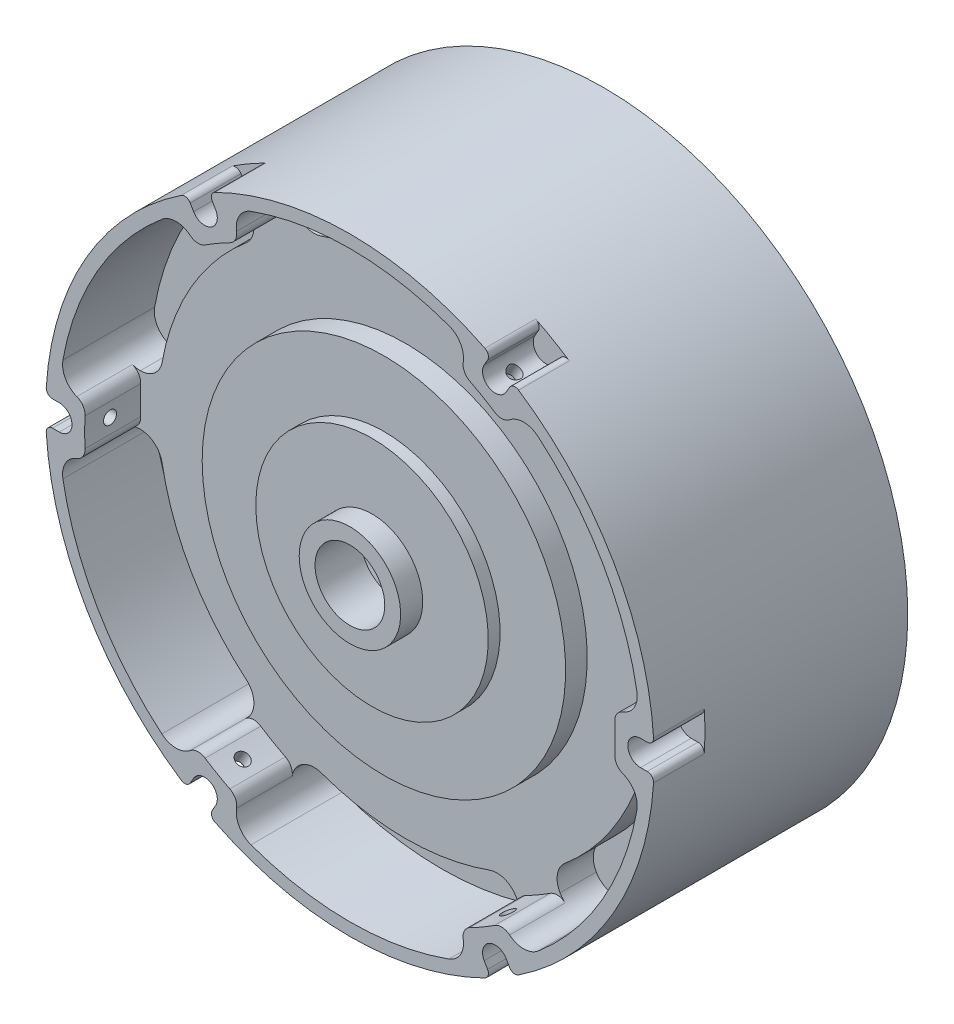
SolidWorks part; units mm, degrees
material "6061-T6 (SS)"
ref_plane "Front Plane" through (0, 0, 0) normal (0, 0, 1) x (1, 0, 0)
ref_plane "Top Plane" through (0, 0, 0) normal (0, 1, 0) x (1, 0, 0)
ref_plane "Right Plane" through (0, 0, 0) normal (1, 0, 0) x (0, 0, -1)
sketch "Sketch2" plane through (0, 0, 0) normal (0, 1, 0) x (1, 0, 0)
  line L0 (0, 11.176) -> (0, 0)
  line L2 (-76.2, 0) -> (-76.2, 46.101)
  line L3 (-76.2, 46.101) -> (-69.85, 46.101) construction
  line L4 (-69.85, 46.101) -> (-34.925, 46.101) construction
  line L5 (-34.925, 46.101) -> (0, 46.101) construction
  line L6 (-76.2, 0) -> (-73.025, 0)
  line L13 (-73.025, 0) -> (-73.025, 22.9805)
  line L14 (-73.025, 22.9805) -> (-61.9125, 22.9805)
  line L15 (-61.9125, 22.9805) -> (-61.9125, 13.9169)
  line L16 (-61.9125, 13.9169) -> (-45.5083, 13.9169)
  line L17 (-45.5083, 13.9169) -> (-45.5083, 8.5103)
  line L18 (-45.5083, 8.5103) -> (-29.1042, 8.5103)
  line L19 (-29.1042, 8.5103) -> (-29.1042, 5.5363)
  line L20 (0, 46.101) -> (0, 11.176) construction
  line L21 (-45.5083, 13.9169) -> (0, 46.101) construction
  line L22 (-61.9125, 22.9805) -> (0, 46.101) construction
  line L23 (0, 46.101) -> (-29.1042, 8.5103) construction
  line L24 (-29.1042, 5.5363) -> (-12.7, 5.5363)
  line L25 (-12.7, 5.5363) -> (-12.7, 0)
  line L26 (-12.7, 0) -> (0, 0)
  line L27 (0, 46.101) -> (-12.7, 5.5363) construction
  line L28 (-69.85, 46.101) -> (-69.85, 63.5)
  line L29 (-69.85, 63.5) -> (-76.2, 63.5)
  line L30 (-76.2, 63.5) -> (-76.2, 46.101)
  ellipse E0 centre (0, 46.101) end of major axis (69.85, 46.101) minor radius 34.925 construction
  ellipse E1 centre (0, 46.101) end of major axis (69.85, 46.101) minor radius 34.925 (-69.85, 46.101) -> (0, 11.176) ccw
  point P2 (-10.8028, 11.5962)
  point P7 (-55.9638, 25.202)
  point P16 (-25.2167, 13.5313)
  point P18 (-40.3238, 17.5834)
  dimension "D3" = 11.176
  dimension "D6" = 6.35
  dimension "D7" = 6.35
  dimension "D11" = 63.5
  dimension "D2" = 76.2
  dimension "D4" = 11.1125
  dimension "D5" = 3.175
  dimension "D8" = 6.35
  dimension "D9" = 6.35
  dimension "D10" = 12.7
  dimension "D12" = 6.35
  dimension "D13" = 52.324
  dimension "D14" = 17.399
revolve "Revolve1" add sketch "Sketch2" angle 360 about L20
sketch "Sketch5" plane through (0, 0, 0) normal (0, 0, 1) x (1, 0, 0)
  circle A0 centre (0, 0) radius 8.7312
  dimension "D1" = 17.4625
extrude "Cut-Extrude2" cut sketch "Sketch5" against normal through all
sketch "Sketch11" plane through (0, 0, 0) normal (0, 0, 1) x (1, 0, 0)
  line L0 (-76.1338, 3.175) -> (-72.771, 3.175)
  line L1 (-76.1338, -3.175) -> (-72.771, -3.175)
  line L2 (-75.935, 6.35) -> (-61.586, 6.35)
  line L3 (-61.586, 6.35) -> (-61.586, -6.35)
  line L4 (-61.586, -6.35) -> (-75.935, -6.35)
  circle A0 centre (0, 0) radius 76.2 construction
  arc A1 (-72.771, -3.175) -> (-72.771, 3.175) centre (-72.771, 0) ccw
  arc A2 (-76.1338, 3.175) -> (-76.1338, -3.175) centre (0, 0) ccw
  circle A3 centre (0, 0) radius 61.9125 construction
  circle A4 centre (0, 0) radius 61.9125 construction
  arc A5 (-76.1338, -3.175) -> (-75.935, -6.35) centre (-76.3902, -4.7848) cw
  arc A6 (-75.935, 6.35) -> (-76.1338, 3.175) centre (-76.5368, 4.794) cw
  point P8 (-69.596, 0)
  point P20 (-76.2, 0)
  circle M6 centre (0, 0) radius 73.025
  circle M7 centre (0, 0) radius 76.2
  dimension "D1" = 6.35
  dimension "D2" = 3.175
  dimension "D3" = 6.604
extrude "Boss-Extrude2" add sketch "Sketch11" against normal up to surface (22.9805 mm away) contours A1 L4 L3 L2 M6 | A1 M6 | A1 L0 L1 M6 M7 region at (-74.59, 0, 0) region at (-66.6747, 0, 0) region at (-71.5476, 0, 0) up to face at (-61.9125, 0, -22.9805)
sketch "Sketch12" plane through (0, 0, 0) normal (0, 0, 1) x (1, 0, 0)
  line L0 (-76.1338, 3.175) -> (-72.771, 3.175)
  line L1 (-76.1338, -3.175) -> (-72.771, -3.175)
  arc A1 (-72.771, 3.175) -> (-72.771, -3.175) centre (-72.771, 0) cw
  arc A3 (-76.1338, -3.175) -> (-76.1338, 3.175) centre (-76.1338, 0) cw
  point P10 (-69.596, 0)
extrude "Cut-Extrude4" cut sketch "Sketch12" against normal blind 12.7
hole_wizard "#30 (0.1285) Diameter Hole1" positions "Sketch13" profile "Sketch14" hole size "#30" standard "ANSI Inch" end condition through all
sketch "Sketch13" plane through (-61.586, 0, 0) normal (1, 0, 0) x (0, 0, -1)
  line L0 (0, 6.35) -> (0, -6.35) construction
  point P0 (6.35, 0)
  dimension "D1" = 6.35
sketch "Sketch14" plane through (-61.586, 0, -6.35) normal (0, 1, 0) x (0, 0, -1)
  line L0 (0, 0) -> (0, 14.614)
  line L1 (0, 14.614) -> (1.6319, 14.614)
  line L2 (1.6319, 14.614) -> (1.6319, 0)
  line L5 (1.6319, 0) -> (0, 0)
  line L11 (0, -6.35) -> (0, 107.95) construction
  dimension "Thru Hole Dia." = 3.2639
  dimension "Thru Hole Depth" = 14.614
fillet "Fillet3" radius 5.5562 4 edges at (-72.7484, -6.35, -11.4902) (-72.7484, 6.35, -11.4902) (-61.586, -6.35, -18.4487) (-61.586, 6.35, -18.4487)
fillet "Fillet5" radius 1.5875 2 edges at (-76.1338, -3.175, -6.35) (-76.1338, 3.175, -6.35)
pattern_circular "CirPattern3" count 6 over 360 about axis through (0, 0, 0) along (0, 0, -1) of "Boss-Extrude2", "Cut-Extrude4", "#30 (0.1285) Diameter Hole1", "Fillet3", "Fillet5"
sketch "Sketch15" plane through (0, 0, 0) normal (0, 0, 1) x (1, 0, 0)
  line L0 (-61.586, 6.35) -> (-61.586, -6.35) construction
  circle A0 centre (0, 0) radius 61.586
  circle A1 centre (0, 0) radius 66.421
  point P4 (-66.421, 0)
  dimension "D1" = 3.175
extrude "Cut-Extrude6" cut sketch "Sketch15" against normal up to surface (13.9169 mm away) up to face at (-45.5083, 0, -13.9169)
fillet "Fillet6" radius 3.175 12 edges at (-66.1168, 6.35, -6.9584) (-66.1168, -6.35, -6.9584) (38.5576, 54.0838, -6.9584) (-38.5576, 54.0838, -6.9584) (-27.5591, 60.4338, -6.9584) (27.5591, 60.4338, -6.9584) (66.1168, -6.35, -6.9584) (66.1168, 6.35, -6.9584) (38.5576, -54.0838, -6.9584) (27.5591, -60.4338, -6.9584) (-27.5591, -60.4338, -6.9584) (-38.5576, -54.0838, -6.9584)
equation "\"beams\"= 6"
equation "\"D1@CirPattern3\"=\"beams\""
